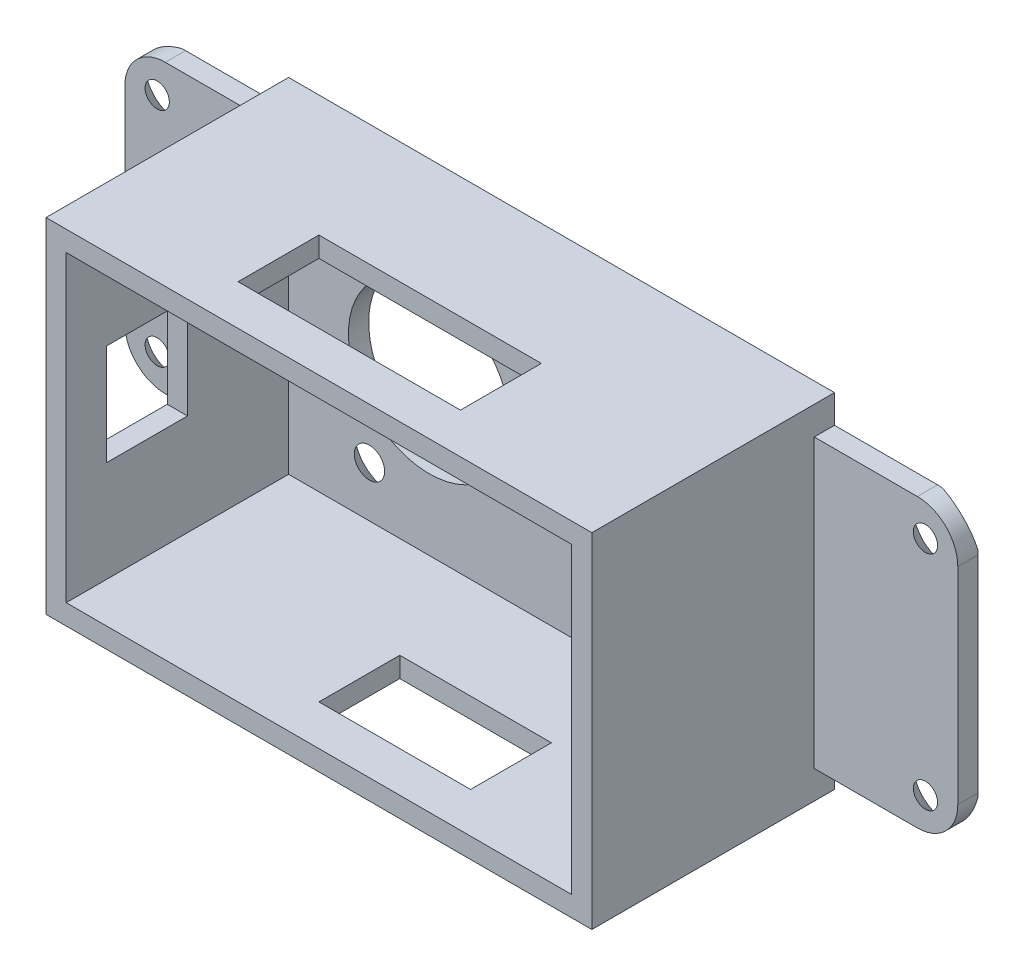
SolidWorks part; units mm, degrees
ref_plane "Plano frontal" through (0, 0, 0) normal (0, 0, 1) x (1, 0, 0)
ref_plane "Plano superior" through (0, 0, 0) normal (0, 1, 0) x (1, 0, 0)
ref_plane "Plano direito" through (0, 0, 0) normal (1, 0, 0) x (0, 0, -1)
sketch "Esboço1" plane through (0, 0, 0) normal (0, 0, 1) x (1, 0, 0)
  line L1 (0, 0) -> (54, 0)
  line L2 (0, 0) -> (0, 34)
  line L3 (0, 34) -> (54, 34)
  line L4 (54, 0) -> (54, 34)
extrude "Ressalto-extrusão1" add sketch "Esboço1" along normal blind 2
sketch "Esboço2" plane through (0, 0, 2) normal (0, 0, 1) x (1, 0, 0)
  line L0 (2, 32) -> (52, 32)
  line L1 (0, 34) -> (54, 34)
  line L2 (0, 34) -> (0, 0)
  line L3 (0, 0) -> (54, 0)
  line L4 (54, 34) -> (54, 0)
  line L5 (52, 32) -> (52, 2)
  line L6 (2, 2) -> (52, 2)
  line L7 (2, 32) -> (2, 2)
  dimension "D1" = 2
extrude "Ressalto-extrusão2" add sketch "Esboço2" along normal blind 22
sketch "Esboço3" plane through (0, 0, 2) normal (0, 0, 1) x (1, 0, 0)
  line L0 (52, 2) -> (52, 32) construction
  circle A0 centre (48, 27) radius 1.5
  circle A1 centre (48, 7) radius 1.5
  dimension "D1" = 4
  dimension "D2" = 4
  dimension "D3" = 20
extrude "Corte-extrusão1" cut sketch "Esboço3" against normal blind 4
sketch "Esboço4" plane through (0, 0, 2) normal (0, 0, 1) x (1, 0, 0)
  line L0 (2, 2) -> (52, 2) construction
  line L1 (52, 32) -> (2, 32) construction
  circle A0 centre (14, 7) radius 1.5
  circle A1 centre (48, 7) radius 1.5 construction
  circle A2 centre (14, 27) radius 1.5
  circle A3 centre (48, 27) radius 1.5 construction
  dimension "D1" = 5
  dimension "D2" = 34
  dimension "D3" = 5
  dimension "D4" = 34
extrude "Corte-extrusão2" cut sketch "Esboço4" against normal blind 4
sketch "Esboço5" plane through (0, 0, 2) normal (0, 0, 1) x (1, 0, 0)
  line L0 (2, 32) -> (2, 2) construction
  circle A0 centre (19.92, 17) radius 7
  dimension "D1" = 17.92
  dimension "D2" = 14
extrude "Corte-extrusão3" cut sketch "Esboço5" against normal blind 4
sketch "Esboço7" plane through (0, 34, 0) normal (0, 1, 0) x (1, 0, 0)
  line L0 (0, -24) -> (0, -20)
  line L1 (0, -24) -> (0, 0) construction
  line L3 (15, -20) -> (15, -12)
  line L4 (15, -12) -> (37, -12)
  line L5 (15, -20) -> (37, -20)
  line L6 (37, -20) -> (37, -12)
  dimension "D1" = 22
  dimension "D2" = 8
  dimension "D4" = 15
extrude "Corte-extrusão4" cut sketch "Esboço7" against normal blind 4 contours L5 L6 L4 L3 region at (26, 34, 16)
sketch "Esboço8" plane through (0, 0, 0) normal (0, -1, 0) x (-1, 0, 0)
  line L1 (-54, -24) -> (-54, 0) construction
  line L2 (0, -24) -> (-54, -24) construction
  line L3 (-38, -20) -> (-38, -12)
  line L4 (-38, -12) -> (-23, -12)
  line L8 (-38, -20) -> (-23, -20)
  line L9 (-23, -20) -> (-23, -12)
  dimension "D1" = 16
  dimension "D2" = 4
  dimension "D3" = 8
  dimension "D4" = 15
extrude "Corte-extrusão5" cut sketch "Esboço8" against normal blind 4
sketch "Esboço9" plane through (0, 0, 0) normal (-1, 0, 0) x (0, 0, 1)
  line L0 (24, 34) -> (24, 0) construction
  line L1 (12, 22) -> (20, 22)
  line L2 (12, 22) -> (12, 12)
  line L3 (12, 12) -> (20, 12)
  line L4 (20, 22) -> (20, 12)
  line L5 (24, 34) -> (0, 34) construction
  line L6 (24, 0) -> (0, 0) construction
  dimension "D1" = 4
  dimension "D2" = 12
  dimension "D3" = 12
extrude "Corte-extrusão6" cut sketch "Esboço9" against normal blind 4
sketch "Esboço10" plane through (0, 0, 0) normal (0, 0, -1) x (-1, 0, 0)
  line L0 (-54, 0) -> (-54, 34)
  line L3 (-54, 34) -> (0, 34)
  line L4 (-69, 17) -> (-69, 34)
  line L5 (-69, 34) -> (15, 34)
  line L6 (15, 34) -> (15, 0)
  line L7 (15, 0) -> (-69, 0)
  line L8 (-69, 0) -> (-69, 17)
  line L9 (0, 34) -> (0, 0)
  line M11 (0, 0) -> (0, 34)
  line M13 (-54, 34) -> (-54, 0)
extrude "Ressalto-extrusão3" add sketch "Esboço10" against normal blind 2 contours L8 L7 L5 L4 M13 | L7 L6 L5 M11 region at (61.5, 17, 0) region at (-7.5, 17, 0)
sketch "Esboço11" plane through (0, 0, 0) normal (0, 0, -1) x (-1, 0, 0)
  line L0 (15, 0) -> (-69, 0) construction
  line L1 (-69, 34) -> (-68.5, 34)
  line L2 (-69, 34) -> (-69, 0)
  line L3 (-69, 0) -> (-68.5, 0)
  line L4 (-68.5, 34) -> (-68.5, 0)
  line L5 (-27, 34) -> (-27, 0) construction
  line L6 (-69, 34) -> (15, 34) construction
  line L7 (15, 0) -> (14.5, 0)
  line L8 (15, 34) -> (14.5, 34)
  line L9 (14.5, 34) -> (14.5, 0)
  line L10 (15, 34) -> (15, 0)
extrude "Corte-extrusão7" cut sketch "Esboço11" against normal blind 4
sketch "Esboço12" plane through (0, 0, 0) normal (0, 0, -1) x (-1, 0, 0)
  circle A0 centre (-65, 28) radius 1.2
  circle A1 centre (-65, 6) radius 1.2
  circle A2 centre (11, 6) radius 1.2
  circle A3 centre (11, 28) radius 1.2
extrude "Corte-extrusão8" cut sketch "Esboço12" against normal blind 4
sketch "Esboço13" plane through (0, 0, 2) normal (0, 0, 1) x (1, 0, 0)
  line L1 (52, 2) -> (52, 32) construction
  line L2 (52, 32) -> (2, 32) construction
  circle A1 centre (44, 27) radius 1.5
  circle A2 centre (44, 7) radius 1.5
  circle A3 centre (10, 27) radius 1.5
  circle A4 centre (10, 7) radius 1.5
  dimension "D1" = 8
  dimension "D2" = 20
  dimension "D3" = 5
  dimension "D4" = 34
  dimension "D5" = 20
  dimension "D6" = 5
  dimension "D7" = 34
  dimension "D8" = 0
  dimension "D9" = 3
  dimension "D10" = 3
  dimension "D11" = 3
  dimension "D12" = 3
extrude "Corte-extrusão9" cut sketch "Esboço13" against normal blind 10
sketch "Esboço14" plane through (0, 0, 2) normal (0, 0, 1) x (1, 0, 0)
  line L1 (11.6645, 29.6318) -> (29.8366, 29.6318)
  line L2 (11.6645, 29.6318) -> (11.6645, 4.8114)
  line L3 (11.6645, 4.8114) -> (29.8366, 4.8114)
  line L4 (29.8366, 29.6318) -> (29.8366, 4.8114)
extrude "Ressalto-extrusão4" add sketch "Esboço14" against normal blind 2
sketch "Esboço15" plane through (0, 0, 2) normal (0, 0, 1) x (1, 0, 0)
  line L1 (46.0585, 29.5432) -> (50.668, 29.5432)
  line L2 (46.0585, 29.5432) -> (46.0585, 3.7477)
  line L3 (46.0585, 3.7477) -> (50.668, 3.7477)
  line L4 (50.668, 29.5432) -> (50.668, 3.7477)
extrude "Ressalto-extrusão5" add sketch "Esboço15" against normal blind 2
sketch "Esboço16" plane through (0, 0, 2) normal (0, 0, 1) x (1, 0, 0)
  circle A0 centre (15.92, 17) radius 8
extrude "Corte-extrusão10" cut sketch "Esboço16" against normal blind 2
sketch "Esboço17" plane through (0, 0, 2) normal (0, 0, 1) x (1, 0, 0)
  line L0 (0, 34) -> (0, 0) construction
  line L1 (-14.5, 34) -> (0, 34)
  line L2 (-14.5, 34) -> (-14.5, 31.2)
  line L3 (-14.5, 31.2) -> (0, 31.2)
  line L4 (0, 34) -> (0, 31.2)
  line L5 (54, 0) -> (54, 34) construction
  line L6 (68.5, 34) -> (54, 34)
  line L7 (68.5, 34) -> (68.5, 31.2)
  line L8 (68.5, 31.2) -> (54, 31.2)
  line L9 (54, 34) -> (54, 31.2)
  line L10 (0, 0) -> (0, 34) construction
  line L11 (68.5, 0) -> (54, 0)
  line L12 (68.5, 0) -> (68.5, 2.8)
  line L13 (68.5, 2.8) -> (54, 2.8)
  line L14 (54, 0) -> (54, 2.8)
  line L15 (-14.5, 0) -> (0, 0)
  line L16 (-14.5, 0) -> (-14.5, 2.8)
  line L17 (-14.5, 2.8) -> (0, 2.8)
  line L18 (0, 0) -> (0, 2.8)
extrude "Corte-extrusão11" cut sketch "Esboço17" against normal blind 10
sketch "Esboço18" plane through (0, 0, 2) normal (0, 0, 1) x (1, 0, 0)
  line L0 (0, 2.8) -> (-14.5, 2.8) construction
  line L1 (-14.5, 31.2) -> (-14.2, 31.2)
  line L2 (-14.5, 31.2) -> (-14.5, 2.8)
  line L3 (-14.5, 2.8) -> (-14.2, 2.8)
  line L4 (-14.2, 31.2) -> (-14.2, 2.8)
  line L5 (54, 31.2) -> (68.5, 31.2) construction
  line L6 (68.5, 2.8) -> (68.2, 2.8)
  line L7 (68.5, 2.8) -> (68.5, 31.2)
  line L8 (68.5, 31.2) -> (68.2, 31.2)
  line L9 (68.2, 2.8) -> (68.2, 31.2)
extrude "Corte-extrusão12" cut sketch "Esboço18" against normal blind 10
fillet "Filete1" radius 4 4 edges at (68.2, 2.8, 1) (68.2, 31.2, 1) (-14.2, 2.8, 1) (-14.2, 31.2, 1)
sketch "Esboço19" plane through (0, 34, 0) normal (0, 1, 0) x (1, 0, 0)
  line L2 (15, -12) -> (37, -12) construction
  line L3 (39, -12) -> (39, -20)
  line L4 (15, -20) -> (37, -20) construction
  line L5 (39, -20) -> (37, -20)
  line L6 (37, -20) -> (37, -12)
  line L7 (37, -12) -> (39, -12)
extrude "Ressalto-extrusão6" add sketch "Esboço19" against normal blind 2
chamfer "Chanfro3" distance 2 angle 45 1 edges at (8.5, 7, 0)
chamfer "Chanfro4" distance 2 angle 45 1 edges at (42.5, 7, 0)
chamfer "Chanfro5" distance 2 angle 45 4 edges at (63.8, 28, 0) (63.8, 6, 0) (8.5, 27, 0) (42.5, 27, 0)
chamfer "Chanfro7" distance 2 angle 45 2 edges at (-9.8, 28, 0) (-9.8, 6, 0)
sketch "Esboço20" plane through (0, 0, 0) normal (0, 0, -1) x (-1, 0, 0)
  line L0 (-64.3416, 17.1706) -> (-63.2533, 16.562)
  line L1 (-58.7756, 18.0603) -> (-56.1015, 18.0603)
  line L2 (-56.1015, 18.0603) -> (-56.0163, 18.7621)
  line L3 (-58.7756, 17.5552) -> (-56.6195, 17.5552)
  line L4 (-56.6195, 15.695) -> (-59.5976, 15.695)
  line L5 (-59.5976, 15.695) -> (-59.4526, 16.3936)
  line L6 (-59.4526, 16.3936) -> (-56.7349, 16.3936)
  line L7 (-56.7349, 16.8663) -> (-58.8823, 16.8663)
  line L8 (-55.1385, 18.7621) -> (-55.1385, 18.0603)
  line L9 (-55.1385, 18.0603) -> (-52.1325, 18.0603)
  line L10 (-55.1385, 18.7621) -> (-52.1325, 18.7725)
  line L11 (-52.0351, 16.707) -> (-54.326, 16.707)
  line L12 (-52.1017, 17.4112) -> (-54.6831, 17.4112)
  line L13 (-55.103, 17) -> (-55.103, 15.695)
  line L14 (-55.103, 15.695) -> (-54.4057, 15.695)
  line L15 (-54.4057, 15.695) -> (-54.4057, 16.5981)
  line L16 (-50.4799, 15.7491) -> (-49.7845, 15.7491)
  line L17 (-49.7845, 15.7491) -> (-49.7845, 17.8288)
  line L18 (-50.4799, 15.7491) -> (-50.4799, 18.0603)
  line L19 (-49.7794, 18.7725) -> (-47.5196, 18.8077)
  line L20 (-49.6095, 18.1216) -> (-47.6898, 18.1216)
  line L21 (-49.7845, 17.9851) -> (-49.7845, 17.8288)
  line L22 (-47.3927, 17.9113) -> (-47.3927, 17.3937)
  line L23 (-47.3927, 17.3937) -> (-49.0316, 17.3937)
  line L24 (-47.3927, 16.707) -> (-47.3927, 15.7491)
  line L25 (-47.3927, 15.7491) -> (-46.7502, 15.7491)
  line L26 (-46.7502, 15.7491) -> (-46.7502, 17.9851)
  line L27 (-49.447, 16.707) -> (-47.3927, 16.707)
  line L28 (-41.7844, 18.9022) -> (-41.7844, 15.7491)
  line L29 (-41.7844, 15.7491) -> (-38.5087, 15.7491)
  line L30 (-38.5087, 15.7491) -> (-38.6799, 16.492)
  line L31 (-38.6799, 16.492) -> (-41.0539, 16.492)
  line L32 (-41.0539, 16.492) -> (-41.0539, 17)
  line L33 (-41.0539, 17) -> (-38.6799, 17)
  line L34 (-38.6799, 17) -> (-38.6799, 17.6977)
  line L35 (-38.6799, 17.6977) -> (-41.0641, 17.6977)
  line L36 (-41.0641, 17.6977) -> (-41.0641, 18.1216)
  line L37 (-41.0641, 18.1216) -> (-38.6799, 18.1216)
  line L38 (-38.6799, 18.1216) -> (-38.5087, 18.9022)
  line L39 (-38.5087, 18.9022) -> (-41.7844, 18.9022)
  line L40 (-45.2287, 17.9113) -> (-45.2287, 16.707)
  line L41 (-45.9816, 17.9851) -> (-45.9816, 16.5981)
  line L42 (-45.0885, 18.855) -> (-42.6203, 18.855)
  line L43 (-42.6203, 18.855) -> (-42.7341, 18.1216)
  line L44 (-42.7341, 18.1216) -> (-45.0458, 18.1216)
  line L45 (-45.0458, 15.7491) -> (-42.5706, 15.7491)
  line L46 (-42.5706, 15.7491) -> (-42.7341, 16.492)
  line L47 (-42.7341, 16.492) -> (-45.0028, 16.492)
  line L48 (-37.0549, 18.9022) -> (-37.0549, 16.707)
  line L49 (-36.7792, 16.492) -> (-34.8387, 16.492)
  line L50 (-34.8387, 16.492) -> (-34.6584, 15.8303)
  line L51 (-34.6584, 15.8303) -> (-37.0549, 15.8303)
  line L52 (-37.7972, 18.0384) -> (-37.7972, 16.492)
  line L53 (-33.8748, 15.8303) -> (-33.1384, 15.8303)
  line L54 (-33.1384, 15.8303) -> (-33.1384, 18.0384)
  line L55 (-33.8748, 15.8303) -> (-33.8748, 18.0384)
  line L56 (-33.1384, 18.9022) -> (-30.8328, 18.9022)
  line L57 (-30.1274, 18.1645) -> (-30.1274, 15.8303)
  line L58 (-30.1274, 15.8303) -> (-30.8328, 15.8303)
  line L59 (-30.8328, 15.8303) -> (-30.8328, 16.8008)
  line L60 (-30.8328, 16.8008) -> (-32.8424, 16.8008)
  line L61 (-30.8328, 18.0733) -> (-30.8328, 17.5001)
  line L62 (-30.8328, 17.5001) -> (-32.3945, 17.5001)
  line L63 (-32.7379, 17.1706) -> (-32.8424, 16.8008)
  line L64 (-32.9628, 18.1953) -> (-31.0274, 18.1953)
  line L65 (-29.3189, 18.1953) -> (-29.3189, 15.8303)
  line L66 (-29.3189, 15.8303) -> (-26.103, 15.8928)
  line L67 (-28.8062, 18.9047) -> (-26.2543, 18.9047)
  line L68 (-28.6145, 18.1953) -> (-28.6145, 17.752)
  line L69 (-28.6145, 17.752) -> (-26.3468, 17.752)
  line L70 (-28.6145, 18.1953) -> (-26.4347, 18.1953)
  line L71 (-28.6145, 17) -> (-28.6145, 16.562)
  line L72 (-28.6145, 16.562) -> (-26.3468, 16.562)
  line L73 (-28.6145, 17) -> (-26.3819, 17)
  spline S0 degree 3 poles (-63.2533, 16.562) (-63.27, 17.3355) (-62.8134, 18.4895) (-61.8075, 19.7594) (-60.143, 20.961) (-58.4895, 21.2574) (-57.3251, 20.9955) knots 0 0 0 0 0.269048 0.436763 0.575079 1 1 1 1
  spline S1 degree 2 poles (-57.3251, 20.9955) (-56.6501, 20.9577) (-57.783, 21.2885) knots 0 0 0 1 1 1
  spline S2 degree 3 poles (-57.783, 21.2885) (-58.3478, 21.448) (-59.8786, 21.5223) (-61.3562, 21.0538) (-62.15, 20.5593) knots 0 0 0 0 0.385959 1 1 1 1
  spline S3 degree 2 poles (-62.15, 20.5593) (-62.7878, 20.1287) (-63.2533, 19.5196) knots 0 0 0 1 1 1
  spline S4 degree 3 poles (-63.5734, 19.0589) (-63.829, 18.7384) (-64.1184, 18.1119) (-64.3126, 17.4503) (-64.3416, 17.1706) knots 0 0 0 0 0.591386 1 1 1 1
  spline S5 degree 3 poles (-63.2533, 19.5196) (-63.8963, 19.5345) (-64.8167, 19.4665) (-66.0828, 19.1678) (-66.929, 18.9063) (-67.5917, 18.3428) (-67.7169, 17.5542) (-67.2012, 16.7096) (-66.0348, 15.7989) (-65.0431, 15.1376) (-64.3416, 14.8272) knots 0 0 0 0 0.199805 0.283822 0.403978 0.472066 0.541254 0.630998 0.76336 1 1 1 1
  spline S6 degree 3 poles (-64.3416, 14.8272) (-64.2712, 13.9778) (-63.5009, 12.6554) (-61.8679, 11.4024) (-60.0314, 10.5971) (-58.6439, 10.7243) (-57.9084, 10.8244) knots 0 0 0 0 0.299756 0.520242 0.730809 1 1 1 1
  spline S7 degree 2 poles (-57.9084, 10.8244) (-57.5529, 10.9113) (-58.0934, 10.9098) knots 0 0 0 1 1 1
  spline S8 degree 3 poles (-58.0934, 10.9098) (-58.5971, 10.9212) (-59.3597, 10.9893) (-60.5189, 11.4122) (-61.8542, 12.2479) (-62.5946, 13.377) (-62.9086, 14.1361) knots 0 0 0 0 0.246282 0.366939 0.598194 1 1 1 1
  spline S9 degree 3 poles (-62.9086, 14.1361) (-62.0702, 13.8838) (-60.7829, 13.2791) (-58.8423, 12.8293) (-57.3089, 12.4659) (-55.7304, 12.1745) (-53.7319, 11.7803) (-52.1581, 11.6857) (-51.1564, 11.599) knots 0 0 0 0 0.217614 0.35086 0.494056 0.609441 0.749784 1 1 1 1
  spline S10 degree 2 poles (-51.1564, 11.599) (-50.5654, 11.5718) (-51.4892, 11.7339) knots 0 0 0 1 1 1
  spline S11 degree 3 poles (-51.4892, 11.7339) (-52.3625, 11.967) (-53.8819, 12.3727) (-56.0772, 13.0645) (-58.0956, 13.7458) (-60.24, 14.47) (-62.6125, 15.5085) (-64.47, 16.252) (-65.8882, 17.6423) (-65.1249, 18.5092) (-64.4017, 18.9352) (-63.8575, 19.1027) (-63.5734, 19.0589) knots 0 0 0 0 0.149433 0.259822 0.380461 0.501236 0.635114 0.801941 0.854496 0.910361 0.953252 1 1 1 1
  spline S12 degree 1 poles (-56.0163, 18.7621) (-58.9388, 18.7725) knots 0 0 1 1
  spline S13 degree 3 poles (-58.9388, 18.7725) (-59.4491, 18.6623) (-59.8685, 17.727) (-59.2484, 16.9749) (-58.8823, 16.8663) knots 0 0 0 0 0.544753 1 1 1 1
  spline S14 degree 3 poles (-58.7756, 18.0603) (-58.9372, 17.9448) (-58.9442, 17.6684) (-58.7756, 17.5552) knots 0 0 0 0 1 1 1 1
  spline S15 degree 3 poles (-56.6195, 17.5552) (-55.7538, 17.4318) (-55.6688, 15.9504) (-56.6195, 15.695) knots 0 0 0 0 1 1 1 1
  spline S16 degree 2 poles (-56.7349, 16.3936) (-56.4361, 16.6117) (-56.7349, 16.8663) knots 0 0 0 1 1 1
  spline S17 degree 3 poles (-52.1325, 18.0603) (-51.862, 17.9365) (-51.9146, 17.57) (-52.1017, 17.4112) knots 0 0 0 0 1 1 1 1
  spline S18 degree 3 poles (-52.1325, 18.7725) (-51.7494, 18.8382) (-51.3898, 18.3746) (-51.2256, 17.4478) (-51.583, 16.8097) (-52.0351, 16.707) knots 0 0 0 0 0.351622 0.539319 1 1 1 1
  spline S19 degree 3 poles (-54.6831, 17.4112) (-54.8881, 17.4085) (-55.1314, 17.2223) (-55.103, 17) knots 0 0 0 0 1 1 1 1
  spline S20 degree 2 poles (-54.326, 16.707) (-54.4364, 16.7225) (-54.4057, 16.5981) knots 0 0 0 1 1 1
  spline S21 degree 3 poles (-50.4799, 18.0603) (-50.4703, 18.4261) (-50.1297, 18.731) (-49.7794, 18.7725) knots 0 0 0 0 1 1 1 1
  spline S22 degree 2 poles (-49.6095, 18.1216) (-49.7726, 18.13) (-49.7845, 17.9851) knots 0 0 0 1 1 1
  spline S23 degree 2 poles (-47.6898, 18.1216) (-47.4089, 18.1473) (-47.3927, 17.9113) knots 0 0 0 1 1 1
  spline S24 degree 2 poles (-49.0316, 17.3937) (-49.4214, 17.1801) (-49.447, 16.707) knots 0 0 0 1 1 1
  spline S25 degree 3 poles (-47.5196, 18.8077) (-47.0574, 18.8418) (-46.7518, 18.3922) (-46.7502, 17.9851) knots 0 0 0 0 1 1 1 1
  spline S26 degree 2 poles (-45.9816, 16.5981) (-45.8606, 15.8425) (-45.0458, 15.7491) knots 0 0 0 1 1 1
  spline S27 degree 2 poles (-45.2287, 16.707) (-45.2401, 16.5084) (-45.0028, 16.492) knots 0 0 0 1 1 1
  spline S28 degree 2 poles (-45.9816, 17.9851) (-45.8149, 18.6855) (-45.0885, 18.855) knots 0 0 0 1 1 1
  spline S29 degree 2 poles (-45.2287, 17.9113) (-45.2254, 18.086) (-45.0458, 18.1216) knots 0 0 0 1 1 1
  spline S30 degree 2 poles (-37.0549, 18.9022) (-37.7837, 18.9011) (-37.7972, 18.0384) knots 0 0 0 1 1 1
  spline S31 degree 2 poles (-37.7972, 16.492) (-37.6666, 15.8861) (-37.0549, 15.8303) knots 0 0 0 1 1 1
  spline S32 degree 2 poles (-37.0549, 16.707) (-37.0474, 16.4053) (-36.7792, 16.492) knots 0 0 0 1 1 1
  spline S33 degree 3 poles (-33.8748, 18.0384) (-33.8493, 18.4329) (-33.5917, 18.9017) (-33.1384, 18.9022) knots 0 0 0 0 1 1 1 1
  spline S34 degree 2 poles (-33.1384, 18.0384) (-33.0883, 18.1557) (-32.9628, 18.1953) knots 0 0 0 1 1 1
  spline S35 degree 2 poles (-30.8328, 18.9022) (-30.2733, 18.7464) (-30.1274, 18.1645) knots 0 0 0 1 1 1
  spline S36 degree 2 poles (-31.0274, 18.1953) (-30.8944, 18.192) (-30.8328, 18.0733) knots 0 0 0 1 1 1
  spline S37 degree 2 poles (-32.3945, 17.5001) (-32.6618, 17.4864) (-32.7379, 17.1706) knots 0 0 0 1 1 1
  spline S38 degree 2 poles (-29.3189, 18.1953) (-29.2676, 18.6731) (-28.8062, 18.9047) knots 0 0 0 1 1 1
  spline S39 degree 3 poles (-26.2543, 18.9047) (-25.9318, 18.8781) (-25.3961, 18.3833) (-25.5469, 17.5903) (-25.869, 17.3937) knots 0 0 0 0 0.454862 1 1 1 1
  spline S40 degree 3 poles (-25.869, 17.3937) (-25.5894, 17.2797) (-25.3544, 16.6079) (-25.6901, 15.9795) (-26.103, 15.8928) knots 0 0 0 0 0.432291 1 1 1 1
  spline S41 degree 3 poles (-26.4347, 18.1953) (-26.2026, 18.2406) (-26.1425, 17.8166) (-26.3468, 17.752) knots 0 0 0 0 1 1 1 1
  spline S42 degree 3 poles (-26.3819, 17) (-26.178, 16.9697) (-26.1217, 16.6243) (-26.3468, 16.562) knots 0 0 0 0 1 1 1 1
extrude "Corte-extrusão13" cut sketch "Esboço20" against normal blind 0.5
